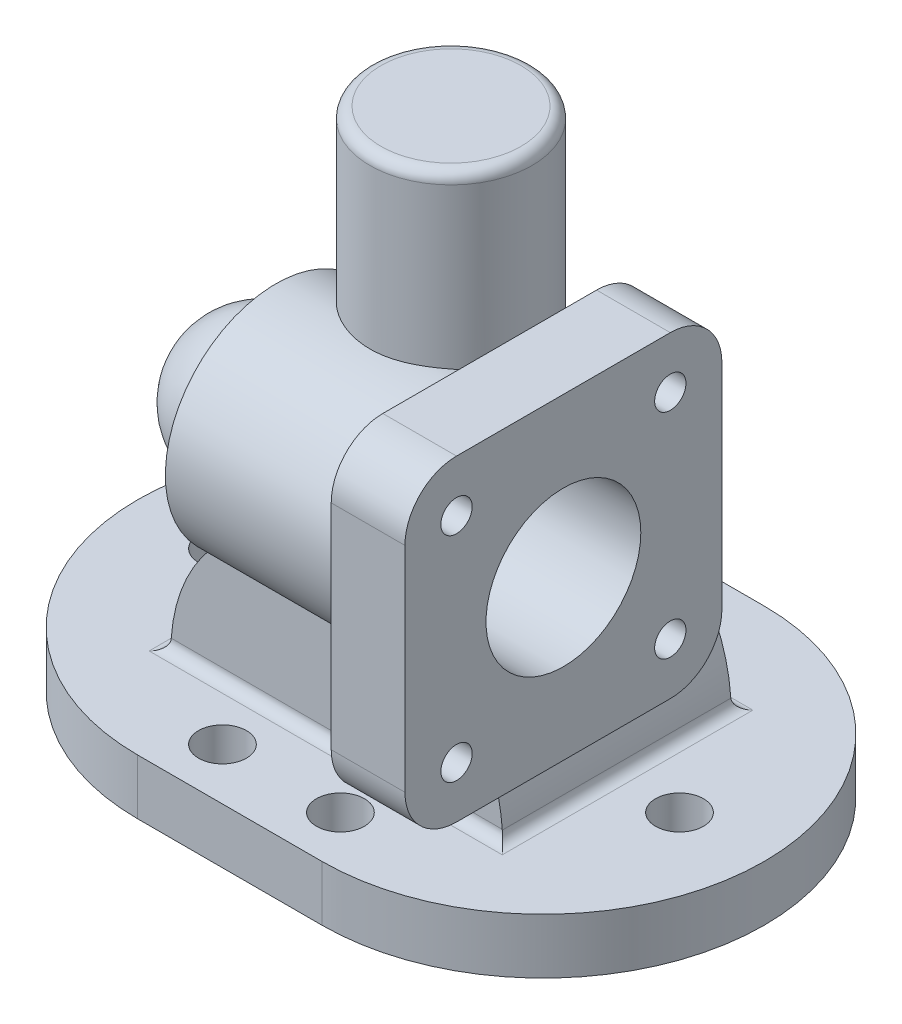
SolidWorks part; units mm, degrees
ref_plane "前视基准面" through (0, 0, 0) normal (0, 0, 1) x (1, 0, 0)
ref_plane "上视基准面" through (0, 0, 0) normal (0, 1, 0) x (1, 0, 0)
ref_plane "右视基准面" through (0, 0, 0) normal (1, 0, 0) x (0, 0, -1)
sketch "草图1" plane through (0, 0, 0) normal (0, 1, 0) x (1, 0, 0)
  line L0 (25, 0) -> (-25, 0) construction
  line L1 (25, -60) -> (-25, -60)
  line L2 (25, 60) -> (-25, 60)
  arc A0 (25, -60) -> (25, 60) centre (25, 0) ccw
  arc A1 (-25, 60) -> (-25, -60) centre (-25, 0) ccw
  point P2 (0, 0)
  dimension "D2" = 60
  dimension "D1" = 50
extrude "凸台-拉伸1" add sketch "草图1" along normal blind 15
sketch "草图2" plane through (0, 0, 0) normal (0, 0, 1) x (1, 0, 0)
  line L0 (-25, 15) -> (25, 15) construction
  line L1 (-25, 15) -> (-85, 15) construction
  line L2 (85, 15) -> (25, 15) construction
  line L3 (-45, 15) -> (45, 15)
  arc A0 (-45, 15) -> (45, 15) centre (0, 15) cw
  arc A1 (-35, 15) -> (35, 15) centre (0, 15) cw
  dimension "D1" = 35
  dimension "D2" = 45
extrude "凸台-拉伸2" add sketch "草图2" along normal mid plane 62 contours L3 A1 A0 | A1 L3 region at (0, 58.9938, 0) region at (0, 29.8545, 0)
sketch "草图3" plane through (0, 0, 0) normal (1, 0, 0) x (0, 0, -1)
  line L0 (-60, 0) -> (60, 0) construction
  line L1 (23.5, 117) -> (-62.5, 117)
  line L2 (23.5, 117) -> (23.5, 31)
  line L3 (23.5, 31) -> (-62.5, 31)
  line L4 (-62.5, 117) -> (-62.5, 31)
  line L5 (23.5, 117) -> (-62.5, 31) construction
  line L6 (23.5, 31) -> (-62.5, 117) construction
  point P0 (-19.5, 74)
  dimension "D1" = 86
  dimension "D2" = 74
  dimension "D3" = 19.5
extrude "凸台-拉伸3" add sketch "草图3" along normal blind 20 from offset 30
sketch "草图4" plane through (30, 0, 0) normal (-1, 0, 0) x (0, 0, 1)
  line L0 (19.5, 117) -> (19.5, 74) construction
  line L1 (-23.5, 117) -> (62.5, 117) construction
  line L2 (19.5, 74) -> (62.5, 74) construction
  line L3 (62.5, 117) -> (62.5, 31) construction
  circle A0 centre (19.5, 74) radius 30
  point P2 (19.5, 74)
  dimension "D1" = 60
extrude "凸台-拉伸4" add sketch "草图4" along normal blind 58
sketch "草图5" plane through (0, 0, 0) normal (0, -1, 0) x (1, 0, 0)
  circle A0 centre (0, 0) radius 22
  dimension "D1" = 44
extrude "凸台-拉伸5" add sketch "草图5" against normal blind 150
sketch "草图6" plane through (-28, 0, 0) normal (-1, 0, 0) x (0, 0, 1)
  circle A0 centre (19.5, 74) radius 20
  dimension "D1" = 40
extrude "凸台-拉伸6" add sketch "草图6" along normal blind 4
dome "圆顶1" faces to dome 1 distance 20 reverse direction no elliptical dome no face at (-32, 74, 39.5) parameters "D1"=20
sketch "草图7" plane through (0, 150, 0) normal (0, 1, 0) x (1, 0, 0)
  circle A0 centre (0, 0) radius 12
  dimension "D1" = 24
extrude "切除-拉伸1" cut sketch "草图7" against normal through all from offset 10 offset against normal yes
sketch "草图8" plane through (50, 0, 0) normal (1, 0, 0) x (0, 0, -1)
  arc A0 (-1.2002, 50.2278) -> (-31, 46.2917) centre (-19.5, 74) ccw construction
  arc A1 (-1.2002, 50.2278) -> (-31, 46.2917) centre (-19.5, 74) ccw construction
  circle A2 centre (-19.5, 74) radius 21
  dimension "D1" = 42
extrude "切除-拉伸2" cut sketch "草图8" against normal blind 65
hole_wizard "大小mm 暗销孔1" positions "3D草图1" profile "草图10" hole size "Ø1.0" standard "GB"
sketch3d "3D草图1"
  circle A0 centre (-15, 74, 19.5) radius 21 construction
  point P0 (-15, 74, 19.5)
  point P5 (6, 74, 19.5)
sketch "草图10" plane through (-15, 74, 19.5) normal (0, 1, 0) x (0, 0, -1)
  line L0 (0, 0) -> (0, 25.4077)
  line L1 (0, 25.4077) -> (9, 20)
  line L2 (9, 20) -> (9, 0)
  line L5 (9, 0) -> (0, 0)
  line L10 (0, 25.4077) -> (-9, 20) construction
  line L11 (0, -6.35) -> (0, 107.95) construction
  dimension "孔直径" = 18
  dimension "孔深度" = 20
  dimension "导头角度" = 118
sketch "草图11" plane through (0, 0, 0) normal (0, 0, 1) x (1, 0, 0)
  line L0 (-25, 15) -> (25, 15) construction
  line L1 (-45, 15) -> (45, 15) construction
  line L2 (85, 15) -> (25, 15) construction
  line L3 (-35, 15) -> (-35, 0)
  line L4 (-85, 0) -> (-25, 0) construction
  line L5 (-35, 0) -> (35, 0)
  line L6 (25, 0) -> (85, 0) construction
  line L7 (35, 0) -> (35, 15)
  arc A0 (-35, 15) -> (35, 15) centre (0, 15) cw
  dimension "D1" = 35
extrude "切除-拉伸3" cut sketch "草图11" against normal mid plane 42
fillet "圆角1" radius 14 4 edges at (46.0297, 31, -23.5) (40, 117, -23.5) (40, 31, 62.5) (40, 117, 62.5)
sketch "草图12" plane through (50, 0, 0) normal (1, 0, 0) x (0, 0, -1)
  line L1 (-48.5, 103) -> (9.5, 103) construction
  line L2 (-48.5, 103) -> (-48.5, 45) construction
  line L3 (-48.5, 45) -> (9.5, 45) construction
  line L4 (9.5, 103) -> (9.5, 45) construction
  line L5 (-48.5, 103) -> (9.5, 45) construction
  line L6 (-48.5, 45) -> (9.5, 103) construction
  point P0 (-19.5, 74)
  dimension "D1" = 58
hole_wizard "M10 螺纹孔1" positions "3D草图2" profile "草图13" tap size "M10" standard "GB" end condition up to next
sketch3d "3D草图2"
  point P0 (50, 103, 48.5)
  point P3 (50, 103, -9.5)
  point P6 (50, 45, -9.5)
  point P9 (50, 45, 48.5)
sketch "草图13" plane through (50, 103, 48.5) normal (0, 1, 0) x (0, 0, -1)
  line L0 (0, 0) -> (0, 20)
  line L1 (0, 20) -> (4.25, 20)
  line L2 (4.25, 20) -> (4.25, 0)
  line L5 (4.25, 0) -> (0, 0)
  line L11 (0, -6.35) -> (0, 107.95) construction
  dimension "通孔螺纹孔钻头直径" = 8.5
  dimension "通孔螺纹孔钻头深度" = 20
cosmetic thread "孔螺蚊线1" parameters "D2"=10
cosmetic thread "孔螺蚊线2" parameters "D2"=10
cosmetic thread "孔螺蚊线3" parameters "D2"=10
cosmetic thread "孔螺蚊线4" parameters "D2"=10
sketch "草图14" plane through (0, 15, 0) normal (0, 1, 0) x (1, 0, 0)
  line L0 (16, 0) -> (-16, 0)
  arc A0 (-16, 46) -> (-16, -46) centre (-16, 0) ccw
  circle A1 centre (-16, 46) radius 6.5
  circle A2 centre (-62, 0) radius 6.5
  circle A3 centre (-16, -46) radius 6.5
  point P5 (0, 0)
  point P12 (-16, 46)
  point P13 (0, 0)
  dimension "D2" = 46
  dimension "D3" = 13
  dimension "D1" = 32
extrude "切除-拉伸4" cut sketch "草图14" against normal through all contours A0 A2 | A3 | A0 A2 | A1 region at (-15.7767, 15, 39.6878) region at (-59.1603, 15, 0) region at (-64.6743, 15, 0) region at (-16.2233, 15, -52.3122)
mirror "镜向1" about plane through (0, 0, 0) normal (1, 0, 0) of "切除-拉伸4"
fillet "圆角2" radius 3 6 edges at (35, 7.5, -21) (-35, 7.5, -21) (35, 7.5, 21) (-35, 7.5, 21) (0, 50, -21) (0, 50, 21)
fillet "圆角3" radius 3 4 edges at (45, 15, 0) (0, 15, 31) (-45, 15, 0) (0, 15, -31)
fillet "圆角4" radius 3 1 edges at (0, 150, -22)
fillet "圆角5" radius 3 1 edges at (1, 46.2917, 31)
